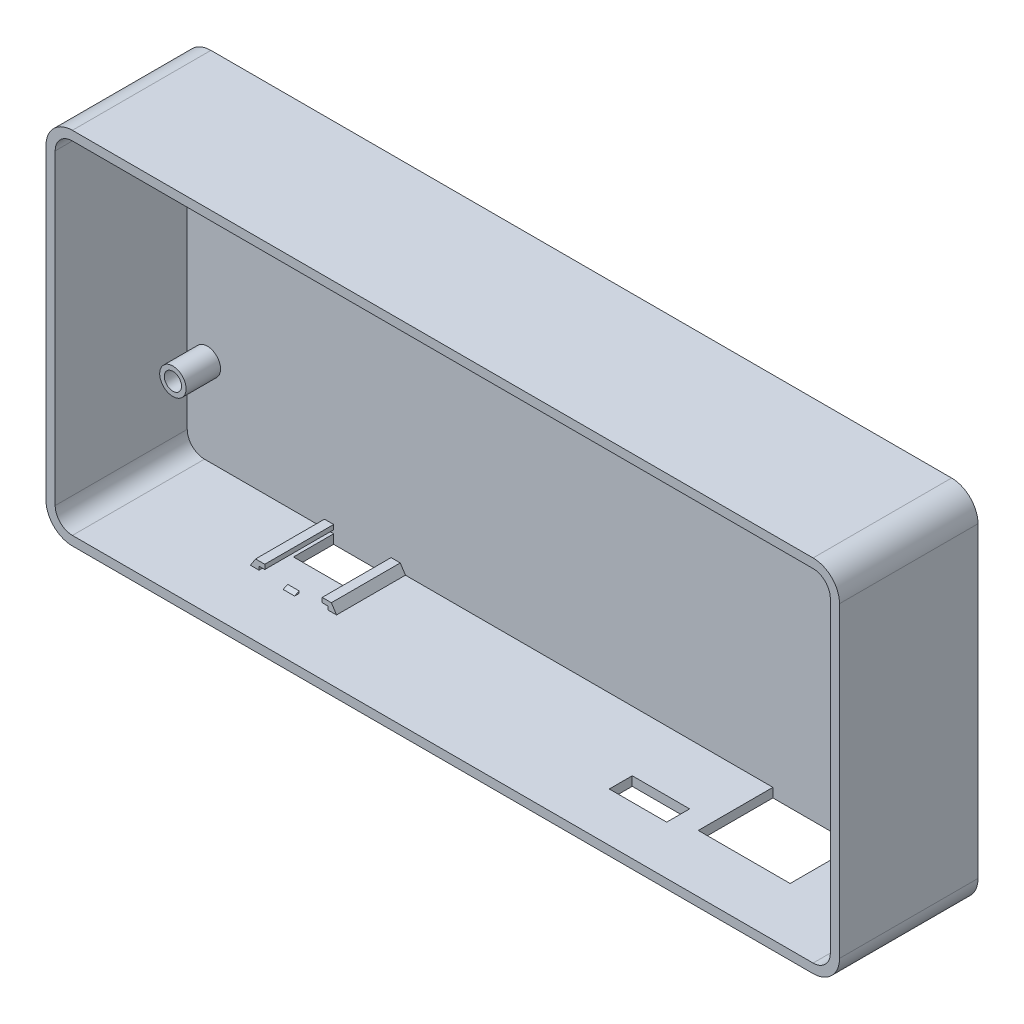
SolidWorks part; units mm, degrees
ref_plane "Alzado" through (0, 0, 0) normal (0, 0, 1) x (1, 0, 0)
ref_plane "Planta" through (0, 0, 0) normal (0, 1, 0) x (1, 0, 0)
ref_plane "Vista lateral" through (0, 0, 0) normal (1, 0, 0) x (0, 0, -1)
sketch "Croquis1" plane through (0, 0, 0) normal (0, 0, 1) x (1, 0, 0)
  line L0 (3, 61.1) -> (132, 61.1)
  line L1 (3, 0) -> (132, 0)
  line L2 (0, 3) -> (0, 56.5)
  line L3 (3, 59.5) -> (132, 59.5)
  line L4 (135, 3) -> (135, 56.5)
  line L5 (136.6, 3) -> (136.6, 56.5)
  line L6 (3, -1.6) -> (132, -1.6)
  line L7 (-1.6, 3) -> (-1.6, 56.5)
  arc A0 (132, 59.5) -> (135, 56.5) centre (132, 56.5) cw
  arc A1 (132, 0) -> (135, 3) centre (132, 3) ccw
  arc A2 (3, 0) -> (0, 3) centre (3, 3) cw
  arc A3 (0, 56.5) -> (3, 59.5) centre (3, 56.5) cw
  arc A4 (132, 61.1) -> (136.6, 56.5) centre (132, 56.5) cw
  arc A5 (132, -1.6) -> (136.6, 3) centre (132, 3) ccw
  arc A6 (3, -1.6) -> (-1.6, 3) centre (3, 3) cw
  arc A7 (-1.6, 56.5) -> (3, 61.1) centre (3, 56.5) cw
  point P9 (135, 0)
  point P12 (0, 0)
  point P15 (0, 59.5)
  dimension "D3" = 3
  dimension "D1" = 135
  dimension "D2" = 59.5
  dimension "D4" = 1.6
extrude "pared" add sketch "Croquis1" along normal blind 23
sketch "Croquis2" plane through (0, -1.6, 0) normal (0, -1, 0) x (1, 0, 0)
  line L0 (0, 23) -> (0, 0) construction
  line L1 (135, 23) -> (135, 0) construction
  line L2 (3, 23) -> (-1.6, 23) construction
  line L3 (-1.6, 23) -> (-1.6, 0) construction
  line L4 (-1.6, 0) -> (3, 0) construction
  line L5 (3, 0) -> (132, 0) construction
  line L6 (132, 0) -> (136.6, 0) construction
  line L7 (136.6, 23) -> (136.6, 0) construction
  line L8 (136.6, 23) -> (132, 23) construction
  line L9 (3, 23) -> (132, 23) construction
  line L10 (0, 23) -> (0, 0)
  line L11 (135, 23) -> (135, 0)
  line L12 (3, 23) -> (-1.6, 23)
  line L13 (-1.6, 23) -> (-1.6, 0)
  line L14 (-1.6, 0) -> (3, 0)
  line L15 (3, 0) -> (132, 0)
  line L16 (132, 0) -> (136.6, 0)
  line L17 (136.6, 23) -> (136.6, 0)
  line L18 (136.6, 23) -> (132, 23)
  line L19 (3, 23) -> (132, 23)
  line L21 (102, 13) -> (118, 13)
  line L22 (102, 13) -> (102, 0)
  line L23 (102, 0) -> (118, 0)
  line L24 (118, 13) -> (118, 0)
  line L25 (88, 14.5) -> (98, 14.5)
  line L26 (88, 14.5) -> (88, 10.5)
  line L27 (88, 10.5) -> (98, 10.5)
  line L28 (98, 14.5) -> (98, 10.5)
  line L29 (25.5, 7) -> (35.5, 7)
  line L30 (25.5, 7) -> (25.5, 0)
  line L31 (25.5, 0) -> (35.5, 0)
  line L32 (35.5, 7) -> (35.5, 0)
  dimension "D1" = 0
  dimension "D2" = 13
  dimension "D3" = 17
  dimension "D4" = 16
  dimension "D5" = 10
  dimension "D6" = 4
  dimension "D7" = 37
  dimension "D8" = 14.5
  dimension "D9" = 7
  dimension "D10" = 10
  dimension "D11" = 109.5
  dimension "D12" = 7
extrude "conectores" cut sketch "Croquis2" against normal up to next contours L24 L21 L22 L23 | L28 L25 L26 L27 | L32 L29 L30 L31 region at (30.5, -1.6, 3.5) region at (110, -1.6, 6.5) region at (93, -1.6, 12.5)
extrude "base frente" add sketch "Croquis1<2>" against normal blind 1.12 contours A6 L7 A7 L0 A4 L5 A5 L6
sketch "Croquis1<2>" plane through (0, 0, 0) normal (0, 0, 1) x (1, 0, 0) same geometry as "Croquis1"
sketch "Croquis3" plane through (0, 0, 0) normal (0, 0, 1) x (1, 0, 0)
  line L4 (135, 3) -> (135, 56.5)
  line L5 (132, 59.5) -> (3, 59.5)
  line L6 (0, 56.5) -> (0, 3)
  line L7 (3, 0) -> (25.5, 0)
  line L8 (135, 3) -> (135, 56.5)
  line L9 (132, 59.5) -> (3, 59.5)
  line L10 (0, 56.5) -> (0, 3)
  line L11 (3, 0) -> (25.5, 0)
  line L24 (130.5, 48) -> (130.5, 41.5) construction
  line L25 (130.5, 28.5) -> (130.5, 17.5) construction
  line L30 (25.5, -1.6) -> (35.5, -1.6)
  line L31 (25.5, -1.6) -> (35.5, -1.6)
  line L32 (102, 0) -> (102, -1.6)
  line L33 (102, 0) -> (102, -1.6)
  line L34 (102, -1.6) -> (118, -1.6)
  line L35 (102, -1.6) -> (118, -1.6)
  line L36 (118, -1.6) -> (118, 0)
  line L37 (118, -1.6) -> (118, 0)
  line L38 (118, 0) -> (132, 0)
  line L39 (118, 0) -> (132, 0)
  line L40 (35.5, -1.6) -> (35.5, 0)
  line L41 (35.5, -1.6) -> (35.5, 0)
  line L42 (35.5, 0) -> (102, 0)
  line L43 (35.5, 0) -> (102, 0)
  line L44 (25.5, 0) -> (25.5, -1.6)
  line L45 (25.5, 0) -> (25.5, -1.6)
  arc A4 (132, 0) -> (135, 3) centre (132, 3) ccw
  arc A5 (135, 56.5) -> (132, 59.5) centre (132, 56.5) ccw
  arc A6 (3, 59.5) -> (0, 56.5) centre (3, 56.5) ccw
  arc A7 (0, 3) -> (3, 0) centre (3, 3) ccw
  arc A8 (132, 0) -> (135, 3) centre (132, 3) ccw
  arc A9 (135, 56.5) -> (132, 59.5) centre (132, 56.5) ccw
  arc A10 (3, 59.5) -> (0, 56.5) centre (3, 56.5) ccw
  arc A11 (0, 3) -> (3, 0) centre (3, 3) ccw
  circle A16 centre (130.5, 48) radius 1.5
  circle A17 centre (130.5, 41.5) radius 1.5
  circle A18 centre (130.5, 35) radius 1.5
  circle A19 centre (130.5, 28.5) radius 1.5
  circle A20 centre (130.5, 17.5) radius 1.5
  circle A21 centre (130.5, 11.5) radius 2.5
  circle A22 centre (130.5, 48) radius 2.3
  circle A23 centre (130.5, 41.5) radius 2.3
  circle A24 centre (130.5, 35) radius 2.3
  circle A25 centre (130.5, 28.5) radius 2.3
  circle A26 centre (130.5, 17.5) radius 2.3
  circle A27 centre (130.5, 11.5) radius 3.3
  circle A28 centre (3.5, 15) radius 1.5
  circle A29 centre (3.5, 15) radius 2.3
  dimension "D8" = 0.8
  dimension "D14" = 3
  dimension "D3" = 5
  dimension "D6" = 3
  dimension "D2" = 6
  dimension "D4" = 0.8
  dimension "D5" = 4
  dimension "D7" = 131.5
  dimension "D12" = 6.5
  dimension "D13" = 11.5
  dimension "D15" = 4.5
  dimension "D17" = 11
  dimension "D9" = 15
  dimension "D1" = 0
  dimension "D16" = 2
extrude "luces" cut sketch "Croquis3" against normal up to next contours A16 | A17 | A18 | A19 | A20 | A21 | A28 region at (130.5, 48, 0) region at (130.5, 41.5, 0) region at (130.5, 35, 0) region at (130.5, 28.5, 0) region at (130.5, 17.5, 0) region at (130.5, 11.5, 0) region at (3.5, 15, 0)
extrude "Saliente-Extruir1" add sketch "Croquis3<3>" along normal blind 12 contours A26 A20 | A25 A19 | A24 A18 | A23 A17 | A22 A16 region at (128.2651, 48, 0) region at (128.2651, 41.5, 0) region at (128.2651, 35, 0) region at (128.2651, 28.5, 0) region at (128.2651, 17.5, 0)
sketch "Croquis3<3>" plane through (0, 0, 0) normal (0, 0, 1) x (1, 0, 0) same geometry as "Croquis3"
extrude "Saliente-Extruir2" add sketch "Croquis3<4>" along normal blind 9 contours A27 A21 region at (127.2933, 11.5, 0)
sketch "Croquis3<4>" plane through (0, 0, 0) normal (0, 0, 1) x (1, 0, 0) same geometry as "Croquis3"
extrude "Saliente-Extruir3" add sketch "Croquis3<5>" along normal blind 6 contours A29 A28 region at (1.2651, 15, 0)
sketch "Croquis3<5>" plane through (0, 0, 0) normal (0, 0, 1) x (1, 0, 0) same geometry as "Croquis3"
sketch "Croquis4" plane through (0, 0, 0) normal (0, 0, 1) x (1, 0, 0)
  line L0 (25.5, 0) -> (35.5, 0) construction
  line L1 (30.5, 0) -> (30.5, 7.3194) construction
  line L2 (36.5, 0) -> (36.5, 0.6)
  line L3 (35.5, 0) -> (102, 0) construction
  line L4 (36.5, 0.6) -> (35.5, 0.6)
  line L5 (35.5, 0.6) -> (35.5, 1.4)
  line L6 (35.5, 1.4) -> (37.1, 1.4)
  line L7 (37.1, 1.4) -> (38, 0)
  line L8 (36.5, 0) -> (38, 0)
  line L9 (24.5, 0) -> (23, 0)
  line L10 (23.9, 1.4) -> (23, 0)
  line L11 (25.5, 1.4) -> (23.9, 1.4)
  line L12 (25.5, 0.6) -> (25.5, 1.4)
  line L13 (24.5, 0.6) -> (25.5, 0.6)
  line L14 (24.5, 0) -> (24.5, 0.6)
  dimension "D1" = 0.6
  dimension "D2" = 0.8
  dimension "D3" = 1
  dimension "D4" = 1.6
  dimension "D5" = 1.5
extrude "Saliente-Extruir4" add sketch "Croquis4" along normal blind 12
sketch "Croquis5" plane through (0, 0, 0) normal (0, 1, 0) x (1, 0, 0)
  line L0 (30.5, -7) -> (30.5, -23) construction
  line L1 (25.5, -7) -> (35.5, -7) construction
  line L2 (3, -23) -> (132, -23) construction
  line L4 (29.5, -12.8) -> (31.5, -12.8)
  line L5 (29.5, -12.8) -> (29.5, -12)
  line L6 (29.5, -12) -> (31.5, -12)
  line L7 (31.5, -12.8) -> (31.5, -12)
  line L8 (29.5, -12.8) -> (31.5, -12) construction
  line L9 (29.5, -12) -> (31.5, -12.8) construction
  point P6 (30.5, -12.4)
  dimension "D1" = 5
  dimension "D2" = 0.8
  dimension "D3" = 2
extrude "Saliente-Extruir5" add sketch "Croquis5" along normal blind 0.4
chamfer "Chaflán1" distance 0.4 angle 65 1 edges at (30.5, 0.4, 12.8) first distance on face at (30.5, 0.2, 12.8)
